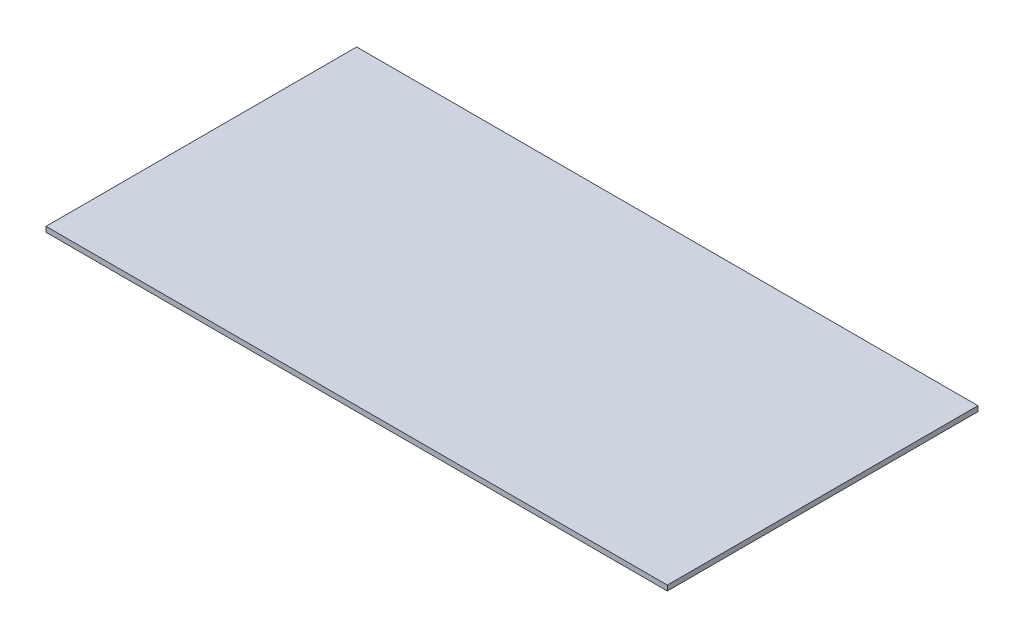
SolidWorks part; units mm, degrees
material "PC High Viscosity"
ref_plane "Front" through (0, 0, 0) normal (0, 0, 1) x (1, 0, 0)
ref_plane "Top" through (0, 0, 0) normal (0, 1, 0) x (1, 0, 0)
ref_plane "Right" through (0, 0, 0) normal (1, 0, 0) x (0, 0, -1)
sketch "Sketch1" plane through (0, 0, 0) normal (0, 1, 0) x (1, 0, 0)
  line L1 (-190.5, -95.25) -> (190.5, -95.25)
  line L2 (-190.5, -95.25) -> (-190.5, 95.25)
  line L3 (-190.5, 95.25) -> (190.5, 95.25)
  line L4 (190.5, -95.25) -> (190.5, 95.25)
  line L5 (-190.5, -95.25) -> (190.5, 95.25) construction
  line L6 (-190.5, 95.25) -> (190.5, -95.25) construction
  point P0 (0, 0)
  dimension "D1" = 190.5
  dimension "D2" = 381
extrude "Boss-Extrude1" add sketch "Sketch1" along normal blind 3.175
